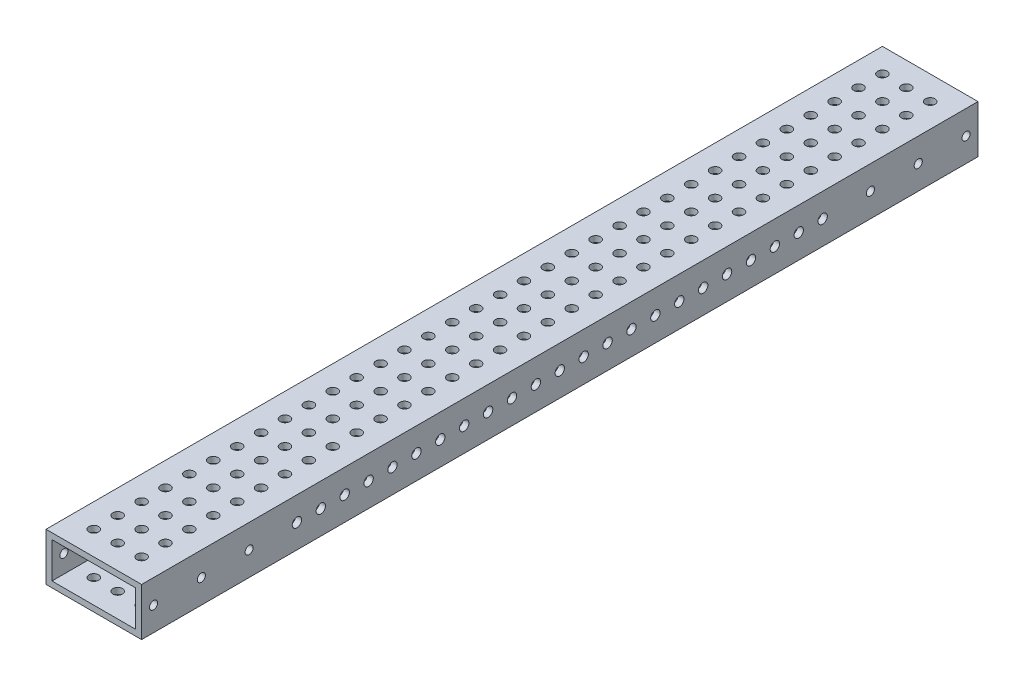
SolidWorks part; units mm, degrees
material "6061-T6 (SS)"
ref_plane "Front Plane" through (0, 0, 0) normal (0, 0, 1) x (1, 0, 0)
ref_plane "Top Plane" through (0, 0, 0) normal (0, 1, 0) x (1, 0, 0)
ref_plane "Right Plane" through (0, 0, 0) normal (1, 0, 0) x (0, 0, -1)
sketch "Sketch1" plane through (0, 0, 0) normal (0, 0, 1) x (1, 0, 0)
  line L0 (-22.225, 9.525) -> (22.225, 9.525)
  line L1 (-25.4, 12.7) -> (25.4, 12.7)
  line L2 (-25.4, 12.7) -> (-25.4, -12.7)
  line L3 (-25.4, -12.7) -> (25.4, -12.7)
  line L4 (25.4, 12.7) -> (25.4, -12.7)
  line L5 (22.225, 9.525) -> (22.225, -9.525)
  line L6 (-22.225, -9.525) -> (22.225, -9.525)
  line L7 (-22.225, 9.525) -> (-22.225, -9.525)
  line L8 (-25.4, 12.7) -> (25.4, -12.7) construction
  line L9 (25.4, 12.7) -> (-25.4, -12.7) construction
  point P5 (0, 0)
  dimension "D1" = 50.8
  dimension "D2" = 25.4
  dimension "D3" = 3.175
extrude "Boss-Extrude1" add sketch "Sketch1" along normal mid plane 444.5
sketch "Sketch2" plane through (0, 12.7, 0) normal (0, 1, 0) x (1, 0, 0)
  line L0 (25.4, -222.25) -> (-25.4, -222.25) construction
  line L1 (-25.4, -222.25) -> (-25.4, 222.25) construction
  line L2 (-12.7, -209.55) -> (0, -209.55) construction
  line L3 (0, -209.55) -> (12.7, -209.55) construction
  line L4 (25.4, 222.25) -> (-25.4, 222.25) construction
  circle A0 centre (0, -209.55) radius 2.5527
  circle A1 centre (12.7, -209.55) radius 2.5527
  circle A2 centre (-12.7, -209.55) radius 2.5527
  circle A3 centre (-12.7, -196.85) radius 2.5527
  circle A4 centre (0, -196.85) radius 2.5527
  circle A5 centre (12.7, -196.85) radius 2.5527
  circle A6 centre (-12.7, -184.15) radius 2.5527
  circle A7 centre (0, -184.15) radius 2.5527
  circle A8 centre (12.7, -184.15) radius 2.5527
  circle A9 centre (-12.7, -171.45) radius 2.5527
  circle A10 centre (0, -171.45) radius 2.5527
  circle A11 centre (12.7, -171.45) radius 2.5527
  circle A12 centre (-12.7, -158.75) radius 2.5527
  circle A13 centre (0, -158.75) radius 2.5527
  circle A14 centre (12.7, -158.75) radius 2.5527
  circle A15 centre (-12.7, -146.05) radius 2.5527
  circle A16 centre (0, -146.05) radius 2.5527
  circle A17 centre (12.7, -146.05) radius 2.5527
  circle A18 centre (-12.7, -133.35) radius 2.5527
  circle A19 centre (0, -133.35) radius 2.5527
  circle A20 centre (12.7, -133.35) radius 2.5527
  circle A21 centre (-12.7, -120.65) radius 2.5527
  circle A22 centre (0, -120.65) radius 2.5527
  circle A23 centre (12.7, -120.65) radius 2.5527
  circle A24 centre (-12.7, -107.95) radius 2.5527
  circle A25 centre (0, -107.95) radius 2.5527
  circle A26 centre (12.7, -107.95) radius 2.5527
  circle A27 centre (-12.7, -95.25) radius 2.5527
  circle A28 centre (0, -95.25) radius 2.5527
  circle A29 centre (12.7, -95.25) radius 2.5527
  circle A30 centre (-12.7, -82.55) radius 2.5527
  circle A31 centre (0, -82.55) radius 2.5527
  circle A32 centre (12.7, -82.55) radius 2.5527
  circle A33 centre (-12.7, -69.85) radius 2.5527
  circle A34 centre (0, -69.85) radius 2.5527
  circle A35 centre (12.7, -69.85) radius 2.5527
  circle A36 centre (-12.7, -57.15) radius 2.5527
  circle A37 centre (0, -57.15) radius 2.5527
  circle A38 centre (12.7, -57.15) radius 2.5527
  circle A39 centre (-12.7, -44.45) radius 2.5527
  circle A40 centre (0, -44.45) radius 2.5527
  circle A41 centre (12.7, -44.45) radius 2.5527
  circle A42 centre (-12.7, -31.75) radius 2.5527
  circle A43 centre (0, -31.75) radius 2.5527
  circle A44 centre (12.7, -31.75) radius 2.5527
  circle A45 centre (-12.7, -19.05) radius 2.5527
  circle A46 centre (0, -19.05) radius 2.5527
  circle A47 centre (12.7, -19.05) radius 2.5527
  circle A48 centre (-12.7, -6.35) radius 2.5527
  circle A49 centre (0, -6.35) radius 2.5527
  circle A50 centre (12.7, -6.35) radius 2.5527
  circle A51 centre (-12.7, 6.35) radius 2.5527
  circle A52 centre (0, 6.35) radius 2.5527
  circle A53 centre (12.7, 6.35) radius 2.5527
  circle A54 centre (-12.7, 19.05) radius 2.5527
  circle A55 centre (0, 19.05) radius 2.5527
  circle A56 centre (12.7, 19.05) radius 2.5527
  circle A57 centre (-12.7, 31.75) radius 2.5527
  circle A58 centre (0, 31.75) radius 2.5527
  circle A59 centre (12.7, 31.75) radius 2.5527
  circle A60 centre (-12.7, 44.45) radius 2.5527
  circle A61 centre (0, 44.45) radius 2.5527
  circle A62 centre (12.7, 44.45) radius 2.5527
  circle A63 centre (-12.7, 57.15) radius 2.5527
  circle A64 centre (0, 57.15) radius 2.5527
  circle A65 centre (12.7, 57.15) radius 2.5527
  circle A66 centre (-12.7, 69.85) radius 2.5527
  circle A67 centre (0, 69.85) radius 2.5527
  circle A68 centre (12.7, 69.85) radius 2.5527
  circle A69 centre (-12.7, 82.55) radius 2.5527
  circle A70 centre (0, 82.55) radius 2.5527
  circle A71 centre (12.7, 82.55) radius 2.5527
  circle A72 centre (-12.7, 95.25) radius 2.5527
  circle A73 centre (0, 95.25) radius 2.5527
  circle A74 centre (12.7, 95.25) radius 2.5527
  circle A75 centre (-12.7, 107.95) radius 2.5527
  circle A76 centre (0, 107.95) radius 2.5527
  circle A77 centre (12.7, 107.95) radius 2.5527
  circle A78 centre (-12.7, 120.65) radius 2.5527
  circle A79 centre (0, 120.65) radius 2.5527
  circle A80 centre (12.7, 120.65) radius 2.5527
  circle A81 centre (-12.7, 133.35) radius 2.5527
  circle A82 centre (0, 133.35) radius 2.5527
  circle A83 centre (12.7, 133.35) radius 2.5527
  circle A84 centre (-12.7, 146.05) radius 2.5527
  circle A85 centre (0, 146.05) radius 2.5527
  circle A86 centre (12.7, 146.05) radius 2.5527
  circle A87 centre (-12.7, 158.75) radius 2.5527
  circle A88 centre (0, 158.75) radius 2.5527
  circle A89 centre (12.7, 158.75) radius 2.5527
  circle A90 centre (-12.7, 171.45) radius 2.5527
  circle A91 centre (0, 171.45) radius 2.5527
  circle A92 centre (12.7, 171.45) radius 2.5527
  circle A93 centre (-12.7, 184.15) radius 2.5527
  circle A94 centre (0, 184.15) radius 2.5527
  circle A95 centre (12.7, 184.15) radius 2.5527
  circle A96 centre (-12.7, 196.85) radius 2.5527
  circle A97 centre (0, 196.85) radius 2.5527
  circle A98 centre (12.7, 196.85) radius 2.5527
  circle A99 centre (-12.7, 209.55) radius 2.5527
  circle A100 centre (0, 209.55) radius 2.5527
  circle A101 centre (12.7, 209.55) radius 2.5527
  circle A108 centre (-12.7, 234.95) radius 2.5527 [skipped]
  circle A109 centre (0, 234.95) radius 2.5527 [skipped]
  circle A110 centre (12.7, 234.95) radius 2.5527 [skipped]
  circle A111 centre (-12.7, 222.25) radius 2.5527 [skipped]
  circle A112 centre (0, 222.25) radius 2.5527 [skipped]
  circle A113 centre (12.7, 222.25) radius 2.5527 [skipped]
  dimension "D2" = 5.1054
  dimension "D4" = 12.7
  dimension "D1" = 12.7
  dimension "D3" = 25.4
  dimension "D6" = 12.7
  dimension "D7" = 12.7
  dimension "D5" = 36
extrude "Cut-Extrude1" cut sketch "Sketch2" against normal through all
sketch "Sketch3" plane through (25.4, 0, 0) normal (1, 0, 0) x (0, 0, -1)
  line L0 (-222.25, -12.7) -> (-222.25, 12.7) construction
  line L1 (-222.25, 12.7) -> (222.25, 12.7) construction
  line L2 (222.25, -12.7) -> (222.25, 12.7) construction
  circle A0 centre (-215.9, 0) radius 2.1527
  circle A1 centre (-190.5, 0) radius 2.1527
  circle A2 centre (-165.1, 0) radius 2.1527
  circle A3 centre (215.9, 0) radius 2.159
  circle A4 centre (190.5, 0) radius 2.159
  circle A5 centre (165.1, 0) radius 2.159
  dimension "D2" = 4.3053
  dimension "D9" = 4.318
  dimension "D1" = 6.35
  dimension "D3" = 12.7
  dimension "D4" = 31.75
  dimension "D5" = 12.7
  dimension "D6" = 57.15
  dimension "D7" = 12.7
  dimension "D8" = 6.35
  dimension "D10" = 12.7
  dimension "D11" = 31.75
  dimension "D12" = 57.15
  dimension "D13" = 12.7
  dimension "D14" = 12.7
extrude "Cut-Extrude2" cut sketch "Sketch3" against normal through all
sketch "Sketch4" plane through (25.4, 0, 0) normal (1, 0, 0) x (0, 0, -1)
  line L1 (-222.25, -12.7) -> (-222.25, 12.7) construction
  line L2 (-222.25, -12.7) -> (222.25, -12.7) construction
  circle A2 centre (-215.9, 0) radius 2.4892 construction
  circle A3 centre (-203.2, 0) radius 2.4892 construction
  circle A16 centre (-190.5, 0) radius 2.4892 construction
  circle A17 centre (-177.8, 0) radius 2.4892 construction
  circle A18 centre (-165.1, 0) radius 2.4892 construction
  circle A35 centre (-152.4, 0) radius 2.4892
  circle A36 centre (-139.7, 0) radius 2.4892
  circle A37 centre (-127, 0) radius 2.4892
  circle A38 centre (-114.3, 0) radius 2.4892
  circle A39 centre (-101.6, 0) radius 2.4892
  circle A40 centre (-88.9, 0) radius 2.4892
  circle A41 centre (-76.2, 0) radius 2.4892
  circle A42 centre (-63.5, 0) radius 2.4892
  circle A43 centre (-50.8, 0) radius 2.4892
  circle A44 centre (-38.1, 0) radius 2.4892
  circle A45 centre (-25.4, 0) radius 2.4892
  circle A46 centre (-12.7, 0) radius 2.4892
  circle A47 centre (0, 0) radius 2.4892
  circle A48 centre (12.7, 0) radius 2.4892
  circle A49 centre (25.4, 0) radius 2.4892
  circle A50 centre (38.1, 0) radius 2.4892
  circle A51 centre (50.8, 0) radius 2.4892
  circle A52 centre (63.5, 0) radius 2.4892
  circle A53 centre (76.2, 0) radius 2.4892
  circle A54 centre (88.9, 0) radius 2.4892
  circle A55 centre (101.6, 0) radius 2.4892
  circle A56 centre (114.3, 0) radius 2.4892
  circle A57 centre (127, 0) radius 2.4892
  circle A58 centre (139.7, 0) radius 2.4892
  circle A59 centre (152.4, 0) radius 2.4892
  circle A60 centre (165.1, 0) radius 2.4892 construction
  circle A61 centre (177.8, 0) radius 2.4892 construction
  circle A62 centre (190.5, 0) radius 2.4892 construction
  circle A63 centre (203.2, 0) radius 2.4892 construction
  point P6 (0, 0)
  dimension "D2" = 4.9784
  dimension "D1" = 6.35
  dimension "D3" = 12.7
  dimension "D4" = 12.7
  dimension "D5" = 34
extrude "Cut-Extrude3" cut sketch "Sketch4" against normal through all contours A36 | A37 | A38 | A39 | A40 | A41 | A42 | A43 | A44 | A45 | A46 | A47 | A48 | A49 | A50 | A51 | A52 | A53 | A54 | A55 | A56 | A57 | A58 region at (25.4, 0, 139.7) region at (25.4, 0, 127) region at (25.4, 0, 114.3) region at (25.4, 0, 101.6) region at (25.4, 0, 88.9) region at (25.4, 0, 76.2) region at (25.4, 0, 63.5) region at (25.4, 0, 50.8) region at (25.4, 0, 38.1) region at (25.4, 0, 25.4) region at (25.4, 0, 12.7) region at (25.4, 0, 0) region at (25.4, 0, -12.7) region at (25.4, 0, -25.4) region at (25.4, 0, -38.1) region at (25.4, 0, -50.8) region at (25.4, 0, -63.5) region at (25.4, 0, -76.2) region at (25.4, 0, -88.9) region at (25.4, 0, -101.6) region at (25.4, 0, -114.3) region at (25.4, 0, -127) region at (25.4, 0, -139.7)
